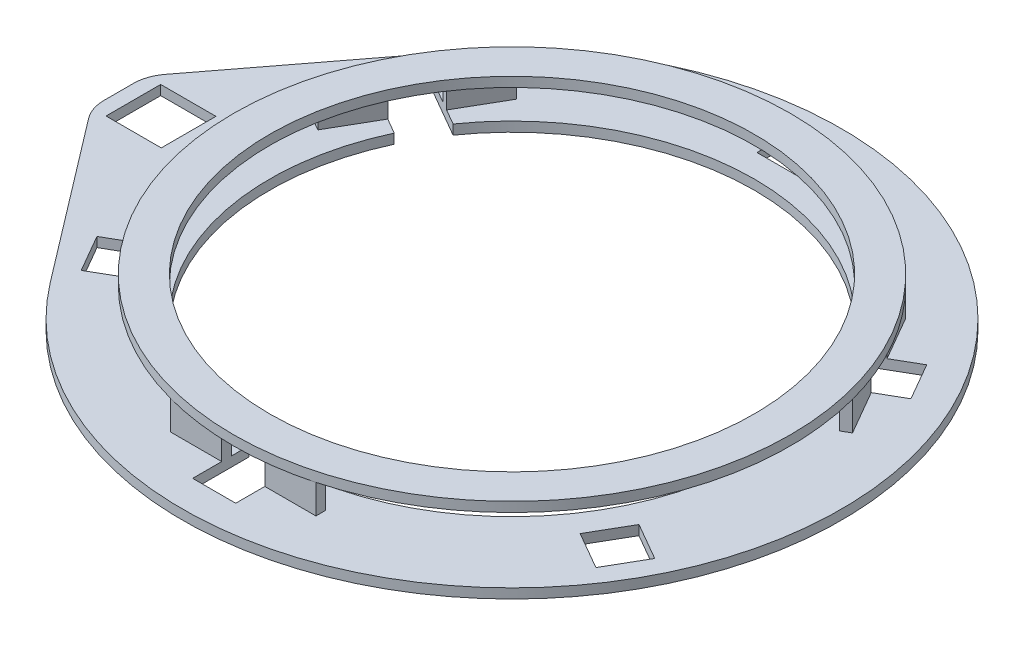
SolidWorks part; units mm, degrees
ref_plane "Front Plane" through (0, 0, 0) normal (0, 0, 1) x (1, 0, 0)
ref_plane "Top Plane" through (0, 0, 0) normal (0, 1, 0) x (1, 0, 0)
ref_plane "Right Plane" through (0, 0, 0) normal (1, 0, 0) x (0, 0, -1)
sketch "Sketch1" plane through (0, 0, 0) normal (0, 1, 0) x (1, 0, 0)
  line L0 (0, 0) -> (430.2979, 0) construction
  line L1 (0, 0) -> (0, 460.2104) construction
  line L2 (0, 319.45) -> (0, 275) construction
  line L3 (-22.225, 319.45) -> (22.225, 319.45)
  line L4 (-22.225, 319.45) -> (-22.225, 275)
  line L5 (-22.225, 275) -> (22.225, 275)
  line L6 (22.225, 319.45) -> (22.225, 275)
  line L7 (287.7643, -140.4776) -> (249.2695, -118.2526)
  line L8 (249.2695, -118.2526) -> (227.0445, -156.7474)
  line L9 (265.5393, -178.9724) -> (227.0445, -156.7474)
  line L10 (287.7643, -140.4776) -> (265.5393, -178.9724)
  line L11 (-265.5393, -178.9724) -> (-227.0445, -156.7474)
  line L12 (-227.0445, -156.7474) -> (-249.2695, -118.2526)
  line L13 (-287.7643, -140.4776) -> (-249.2695, -118.2526)
  line L14 (-265.5393, -178.9724) -> (-287.7643, -140.4776)
  circle A0 centre (0, 0) radius 250
  circle A1 centre (0, 0) radius 340
  dimension "D1" = 500
  dimension "D5" = 680
  dimension "D2" = 44.45
  dimension "D3" = 44.45
  dimension "D4" = 275
  dimension "D6" = 3
extrude "Boss-Extrude1" add sketch "Sketch1" along normal blind 10
sketch "Sketch2" plane through (0, 10, 0) normal (0, 1, 0) x (1, 0, 0)
  line L0 (0, 0) -> (0, -290) construction
  line L1 (0, -281.959) -> (21.6343, -281.959) construction
  line L2 (21.6343, -281.959) -> (26.2932, -277.3) construction
  line L3 (26.2932, -277.3) -> (22.25, -277.3) construction
  line L4 (22.25, -277.3) -> (22.25, -251.9) construction
  line L5 (22.25, -251.9) -> (0, -251.9) construction
  line L6 (22.25, -267.3) -> (-22.25, -267.3)
  line L7 (22.25, -277.3) -> (75, -277.3)
  line L8 (22.25, -277.3) -> (22.25, -267.3) construction
  line L9 (22.25, -267.3) -> (75, -267.3)
  line L10 (75, -277.3) -> (75, -267.3)
  line L11 (22.25, -277.3) -> (-22.25, -277.3)
  line L12 (-75, -277.3) -> (-75, -267.3)
  line L13 (-22.25, -267.3) -> (-75, -267.3)
  line L14 (-22.25, -277.3) -> (-75, -277.3)
  line L15 (-229.0238, 157.9191) -> (-202.6488, 203.6019)
  line L16 (-220.3636, 152.9191) -> (-193.9886, 198.6019)
  line L17 (-242.6136, 114.3809) -> (-220.3636, 152.9191)
  line L18 (-242.6136, 114.3809) -> (-268.9886, 68.6981)
  line L19 (-251.2738, 119.3809) -> (-277.6488, 73.6981)
  line L20 (-277.6488, 73.6981) -> (-268.9886, 68.6981)
  line L21 (-251.2738, 119.3809) -> (-229.0238, 157.9191)
  line L22 (-202.6488, 203.6019) -> (-193.9886, 198.6019)
  line L23 (251.2738, 119.3809) -> (277.6488, 73.6981)
  line L24 (242.6136, 114.3809) -> (268.9886, 68.6981)
  line L25 (220.3636, 152.9191) -> (242.6136, 114.3809)
  line L26 (220.3636, 152.9191) -> (193.9886, 198.6019)
  line L27 (229.0238, 157.9191) -> (202.6488, 203.6019)
  line L28 (202.6488, 203.6019) -> (193.9886, 198.6019)
  line L29 (229.0238, 157.9191) -> (251.2738, 119.3809)
  line L30 (277.6488, 73.6981) -> (268.9886, 68.6981)
  circle A0 centre (0, 0) radius 290 construction
  circle A1 centre (0, 0) radius 250 construction
  circle A2 centre (0, -274.9187) radius 15.0813 construction
  point P22 (0, -267.3)
  point P23 (0, -277.3)
  dimension "D1" = 40
  dimension "D2" = 30.1625
  dimension "D3" = 38.1
  dimension "D4" = 12.7
  dimension "D5" = 22.25
  dimension "D6" = 10
  dimension "D7" = 75
  dimension "D8" = 3
extrude "Boss-Extrude2" add sketch "Sketch2" along normal blind 40
sketch "Sketch3" plane through (0, 0, 277.3) normal (0, 0, 1) x (1, 0, 0)
  line L0 (0, 10) -> (0, 50) construction
  line L1 (-75, 10) -> (75, 10) construction
  line L2 (-75, 50) -> (75, 50) construction
  line L3 (0, 11.6991) -> (-65.6975, 11.6991) construction
  line L4 (22.225, 38.9241) -> (-22.225, 38.9241)
  line L5 (0, 21.6991) -> (-65.6975, 21.6991) construction
  line L6 (22.225, -5.5259) -> (-22.225, -5.5259)
  line L7 (-22.225, 38.9241) -> (-22.225, -5.5259)
  line L8 (0, 16.6991) -> (-22.225, 16.6991) construction
  line L9 (22.225, 38.9241) -> (22.225, -5.5259)
  point P17 (0, -5.5259)
  point P18 (0, 38.9241)
  dimension "D1" = 22.225
  dimension "D2" = 44.45
  dimension "D4" = 10
  dimension "D5" = 5
  dimension "D6" = 22.225
extrude "Cut-Extrude1" cut sketch "Sketch3" against normal mid plane 60
ref_axis "Axis1" through (0, 52.7763, 0) along (0, -1, 0)
pattern_circular "CirPattern1" count 3 over 360 about axis through (0, 52.7763, 0) along (0, -1, 0) of "Cut-Extrude1"
sketch "Sketch4" plane through (0, 50, 0) normal (0, 1, 0) x (1, 0, 0)
  circle A0 centre (0, 0) radius 287.2635
  circle A1 centre (0, 0) radius 250
  dimension "D1" = 500
extrude "Boss-Extrude3" add sketch "Sketch4" against normal blind 10
sketch "Sketch5" plane through (0, 0, 0) normal (0, 1, 0) x (1, 0, 0)
  line L0 (-397.5107, 39.3769) -> (-270.391, 206.1279)
  line L1 (0, 0) -> (-558.2248, 0) construction
  line L2 (-270.391, 206.1279) -> (-330.8791, 0)
  line L3 (-397.5107, -39.3769) -> (-270.391, -206.1279)
  line L4 (-270.391, -206.1279) -> (-330.8791, 0)
  line L5 (-405.7, 15.1266) -> (-405.7, -15.1266)
  line L6 (-390.7, 23.57) -> (-390.7, -23.57) construction
  line L7 (-390.7, 0) -> (-390.7, 28.2)
  line L8 (-390.7, 28.2) -> (-333.7, 28.2)
  line L9 (-333.7, 28.2) -> (-333.7, -28.2)
  line L10 (-333.7, -28.2) -> (-390.7, -28.2)
  line L11 (-390.7, -28.2) -> (-390.7, 0)
  line L12 (-338.93, 28.2) -> (-386.07, 28.2) construction
  line L13 (-386.07, -28.2) -> (-338.93, -28.2) construction
  circle A0 centre (0, 0) radius 340 construction
  arc A1 (-397.5107, -39.3769) -> (-405.7, -15.1266) centre (-365.7, -15.1266) cw
  arc A3 (-397.5107, 39.3769) -> (-405.7, 15.1266) centre (-365.7, 15.1266) ccw
  point P17 (-405.7, -28.6345)
  point P20 (-405.7, 28.6345)
  dimension "D2" = 40
  dimension "D1" = 15
  dimension "D3" = 57
extrude "Boss-Extrude4" add sketch "Sketch5" along normal blind 10
sketch "Sketch6" plane through (0, 10, 0) normal (0, 1, 0) x (-1, 0, 0)
  line L0 (390.7, -28.2) -> (390.7, 28.2)
  line L1 (390.7, 28.2) -> (333.7, 28.2)
  line L2 (333.7, 28.2) -> (333.7, -28.2)
  line L3 (333.7, -28.2) -> (390.7, -28.2)
  dimension "D1" = 57
extrude "Cut-Extrude2" cut sketch "Sketch6" against normal blind 10
